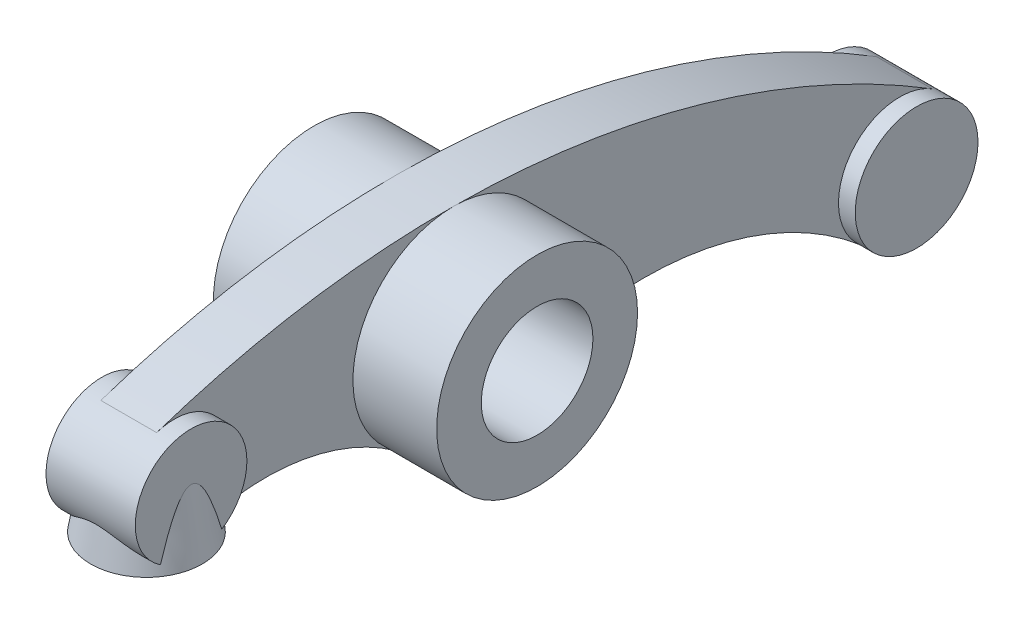
SolidWorks part; units mm, degrees
ref_plane "Front Plane" through (0, 0, 0) normal (0, 0, 1) x (1, 0, 0)
ref_plane "Top Plane" through (0, 0, 0) normal (0, 1, 0) x (1, 0, 0)
ref_plane "Right Plane" through (0, 0, 0) normal (1, 0, 0) x (0, 0, -1)
sketch "Sketch1" plane through (0, 0, 0) normal (1, 0, 0) x (0, 0, -1)
  circle A0 centre (0, 0) radius 9
  circle A1 centre (0, 0) radius 5
  circle A2 centre (-25, 0) radius 5
  circle A3 centre (40, -8) radius 5.5
  arc A4 (-26.5873, 4.7414) -> (42.8942, -3.3231) centre (-0.4429, -73.3554) cw
  arc A5 (-23.364, -4.7248) -> (-5.22, -7.3315) centre (-16.82, -23.6239) cw
  arc A6 (3.9331, -8.0951) -> (36.4434, -12.1953) centre (17.0436, -35.0787) cw
  dimension "D1" = 18
  dimension "D2" = 10
  dimension "D3" = 10
  dimension "D4" = 11
  dimension "D8" = 20
  dimension "D9" = 30
  dimension "D5" = 25
  dimension "D6" = 40
  dimension "D7" = 8
extrude "Boss-Extrude1" add sketch "Sketch1" along normal mid plane 8 contours A2 | A3 region at (0, 0, 25) region at (0, -8, -40)
extrude "Boss-Extrude2" add sketch "Sketch1<4>" along normal mid plane 5 contours A2 A5 A0 A4 | A0 A6 A3 A4 region at (0, 2.298, 13.9555) region at (0, -0.2263, -21.2879)
sketch "Sketch1<4>" plane through (0, 0, 0) normal (1, 0, 0) x (0, 0, -1) same geometry as "Sketch1"
extrude "Boss-Extrude3" add sketch "Sketch1<5>" along normal mid plane 20 contours A0 A1 region at (0, 2.6877, 8.3222)
sketch "Sketch1<5>" plane through (0, 0, 0) normal (1, 0, 0) x (0, 0, -1) same geometry as "Sketch1"
ref_plane "Plane1" through (0, -5, 0) normal (0, 1, 0) x (1, 0, 0)
sketch "Sketch2" plane through (0, -5, 0) normal (0, 1, 0) x (1, 0, 0)
  line L0 (-4, -30) -> (4, -30) construction
  circle A0 centre (0, -25) radius 5
  dimension "D1" = 10
  dimension "D2" = 25
extrude "Boss-Extrude4" add sketch "Sketch2" along normal blind 6 draft 10
